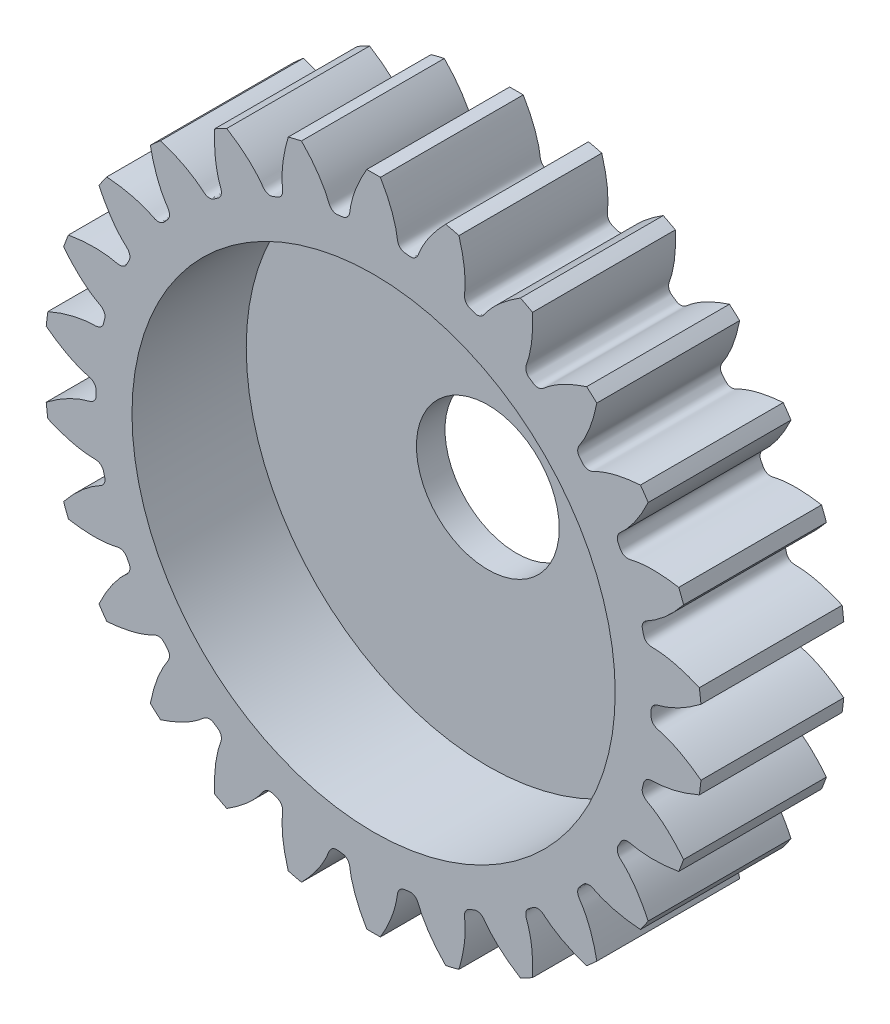
SolidWorks part; units mm, degrees
material "Д16 ГОСТ 4784-97"
ref_plane "FRONT" through (0, 0, 0) normal (0, 0, 1) x (1, 0, 0)
ref_plane "TOP" through (0, 0, 0) normal (0, 1, 0) x (1, 0, 0)
ref_plane "RIGHT" through (0, 0, 0) normal (1, 0, 0) x (0, 0, -1)
ref_axis "Ось1" through (0, 0, 50) along (0, 0, -1)
sketch "SketchRevolveSpurAssemblyNew2Pinion" plane through (0, 0, 0) normal (1, 0, 0) x (0, 0, -1)
  line L0 (0, 0) -> (1, 0) construction
  line L1 (-4, 0) -> (-4, 13.8221)
  line L2 (-4, 13.8221) -> (2, 13.8221)
  line L3 (2, 13.8221) -> (2, 0)
  line L4 (2, 0) -> (-4, 0)
  dimension "D1" = 4
  dimension "D2" = 6
revolve "SpurAssemblyNew2Pinion" add sketch "SketchRevolveSpurAssemblyNew2Pinion" angle 360 about L0
sketch "SketchToothSpurAssemblyNew2Pinion" plane through (0, 0, 0) normal (0, 0, 1) x (1, 0, 0)
  arc A0 (13.8145, 1.4289) -> (13.8145, -1.4289) centre (0, 0) cw
  spline S0 degree 3 poles (13.8145, -1.4289) (13.7267, -1.3599) (13.5952, -1.2613) (13.4189, -1.1388) (13.2926, -1.0553) (13.1699, -0.9783) (13.051, -0.9075) (12.9361, -0.8427) (12.8254, -0.7837) (12.7191, -0.7302) (12.6175, -0.6819) (12.5207, -0.6387) (12.4289, -0.6003) (12.3422, -0.5664) (12.2609, -0.5368) (12.185, -0.5112) (12.1147, -0.4893) (12.0271, -0.4637) (11.9541, -0.4482) (11.8978, -0.428) (11.8759, -0.419) (11.8534, -0.4085) (11.8302, -0.3959) (11.806, -0.3807) (11.7805, -0.3619) (11.7539, -0.3382) (11.7266, -0.3079) (11.7001, -0.2694) (11.6771, -0.2215) (11.6616, -0.1665) (11.6562, -0.0913) (11.6603, 0) (11.6562, 0.0913) (11.6616, 0.1665) (11.6771, 0.2215) (11.7001, 0.2694) (11.7266, 0.3079) (11.7539, 0.3382) (11.7805, 0.3619) (11.806, 0.3807) (11.8302, 0.3959) (11.8534, 0.4085) (11.8759, 0.419) (11.8978, 0.428) (11.9541, 0.4482) (12.0271, 0.4637) (12.1147, 0.4893) (12.185, 0.5112) (12.2609, 0.5368) (12.3422, 0.5664) (12.4289, 0.6003) (12.5207, 0.6387) (12.6175, 0.6819) (12.7191, 0.7302) (12.8254, 0.7837) (12.9361, 0.8427) (13.051, 0.9075) (13.1699, 0.9783) (13.2926, 1.0553) (13.4189, 1.1388) (13.5952, 1.2613) (13.7267, 1.3599) (13.8145, 1.4289) knots 0 0 0 0 0.061766 0.090857 0.118755 0.145459 0.170969 0.195285 0.218406 0.240334 0.261068 0.280608 0.298954 0.316106 0.332064 0.346827 0.360397 0.372773 0.397299 0.401522 0.405868 0.410405 0.415225 0.420444 0.426212 0.432709 0.440141 0.448702 0.45849 0.469388 0.4801 0.5 0.5199 0.530612 0.54151 0.551298 0.559859 0.567291 0.573788 0.579556 0.584775 0.589595 0.594132 0.598478 0.602701 0.627227 0.639603 0.653173 0.667936 0.683894 0.701046 0.719392 0.738932 0.759666 0.781594 0.804715 0.829031 0.854541 0.881245 0.909143 0.938234 1 1 1 1
extrude "ToothExtrudeCutSpurAssemblyNew2Pinion" cut sketch "SketchToothSpurAssemblyNew2Pinion" against normal blind 4 and the other way blind 4
pattern_circular "PatternSpurAssemblyNew2Pinion" count 26 every 13.846 about axis through (0, 0, 50) along (0, 0, -1) of "ToothExtrudeCutSpurAssemblyNew2Pinion"
sketch "AuxiliarySketchSpurAssemblyNew2Pinion" plane through (0, 0, 0) normal (0, 0, 1) x (1, 0, 0)
  circle A0 centre (0, 0) radius 12.5 construction
  circle A1 centre (0, 0) radius 11.7462 construction
  circle A2 centre (0, 0) radius 11.9829 construction
  circle A3 centre (0, 0) radius 13.8221 construction
  circle A4 centre (0, 0) radius 11.6587 construction
  dimension "PitchDiameter" = 25
  dimension "BaseDiameter" = 23.4923
  dimension "FormDiameter" = 23.9658
  dimension "MajorDiameter" = 27.6442
  dimension "MinorDiameter" = 23.3173
sketch "Эскиз3" plane through (0, 0, -2) normal (0, 0, -1) x (-1, 0, 0)
  circle A0 centre (0, 0) radius 9.5
sketch "Эскиз2" plane through (0, 0, 4) normal (0, 0, 1) x (1, 0, 0)
  circle A0 centre (0, 0) radius 10.15
extrude "Вырез-Вытянуть2" cut sketch "Эскиз2" against normal blind 4.8
sketch "Эскиз1" plane through (0, 0, -0.8) normal (0, 0, 1) x (1, 0, 0)
  circle A0 centre (0, 0) radius 7 construction
  circle A1 centre (0, 0) radius 8.25 construction
  circle A2 centre (0, 7) radius 1.25
  circle A3 centre (7, 0) radius 1.25
  circle A4 centre (0, -7) radius 1.25
  circle A5 centre (-7, 0) radius 1.25
  dimension "D1" = 14
  dimension "D2" = 16.5
sketch "Эскиз4" plane through (0, 0, -0.8) normal (0, 0, 1) x (1, 0, 0)
  circle A0 centre (0, 0) radius 3
  dimension "D1" = 6
extrude "Вырез-Вытянуть3" cut sketch "Эскиз4" against normal through all
